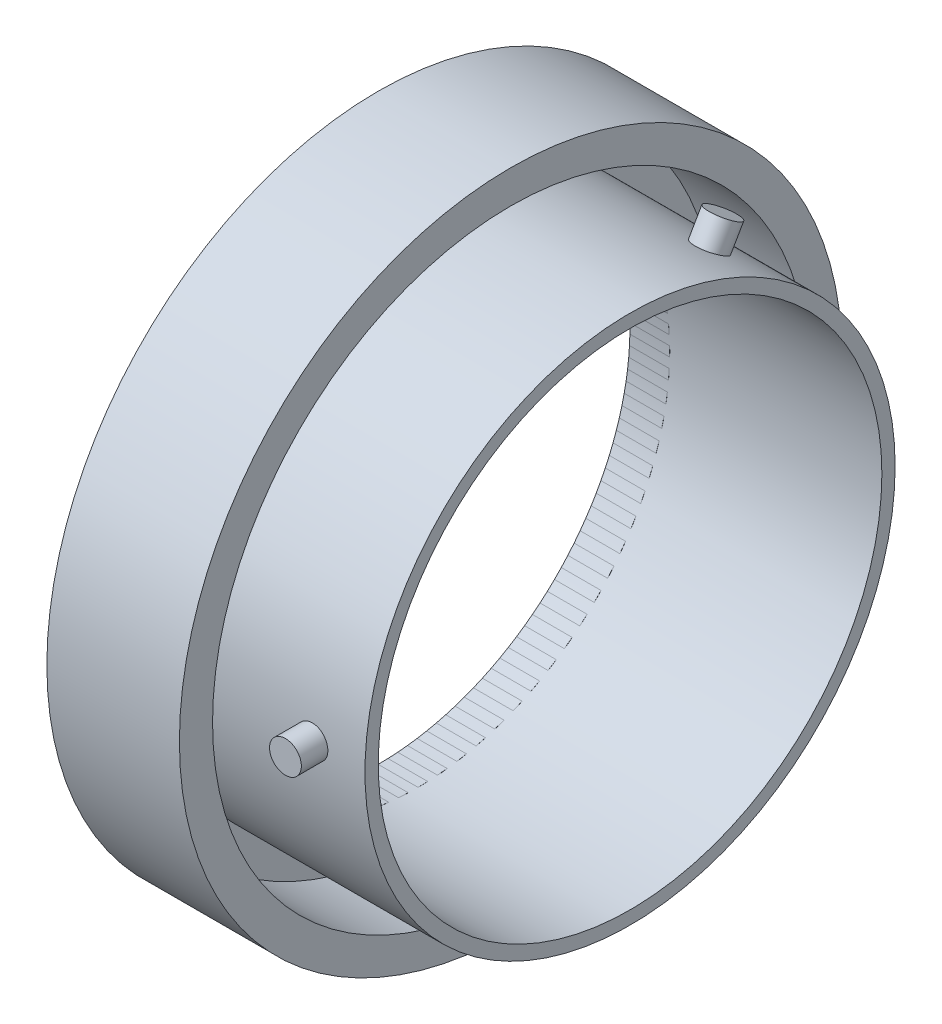
SolidWorks part; units mm, degrees
material "ABS"
ref_plane "Front Plane" through (0, 0, 0) normal (0, 0, 1) x (1, 0, 0)
ref_plane "Top Plane" through (0, 0, 0) normal (0, 1, 0) x (1, 0, 0)
ref_plane "Right Plane" through (0, 0, 0) normal (1, 0, 0) x (0, 0, -1)
sketch "Sketch1" plane through (0, 0, 0) normal (1, 0, 0) x (0, 0, -1)
  circle A0 centre (0, 0) radius 40
  circle A1 centre (0, 0) radius 38
  dimension "D1" = 76
  dimension "D2" = 80
extrude "Boss-Extrude1" add sketch "Sketch1" along normal blind 38
sketch "Sketch2" plane through (0, 0, 0) normal (0, 0, 1) x (1, 0, 0)
  circle A0 centre (30, 0) radius 2.4
  dimension "D1" = 4.8
  dimension "D2" = 30
extrude "Boss-Extrude3" add sketch "Sketch2" along normal blind 44 contours A0
pattern_circular "CirPattern1" count 3 over 360 about axis through (38, 0, 0) along (1, 0, 0) of "Boss-Extrude3"
extrude "Cut-Extrude2" cut sketch "Sketch1<3>" along normal through all contours A1 region at (0, 0, 0)
sketch "Sketch1<3>" plane through (0, 0, 0) normal (1, 0, 0) x (0, 0, -1) same geometry as "Sketch1"
sketch "Sketch3" plane through (0, 0, 0) normal (-1, 0, 0) x (0, 0, 1)
  circle A0 centre (0, 0) radius 40 construction
  circle A1 centre (0, 0) radius 40
  circle A3 centre (0, 0) radius 45
  circle A5 centre (0, 0) radius 50 construction
  circle A7 centre (0, 0) radius 50
  circle M2 centre (0, 0) radius 40
  circle M3 centre (0, 0) radius 38
  dimension "D1" = 90
extrude "Boss-Extrude4" add sketch "Sketch3" against normal blind 20 separate body contours A7 A3 region at (0, 0, -48.5858)
extrude "Boss-Extrude5" add sketch "Sketch3<4>" against normal blind 6 contours A3 M2 | M2 M3 region at (0, 0, -38.8686) region at (0, 0, -43.7272)
sketch "Sketch3<4>" plane through (0, 0, 0) normal (-1, 0, 0) x (0, 0, 1) same geometry as "Sketch3"
